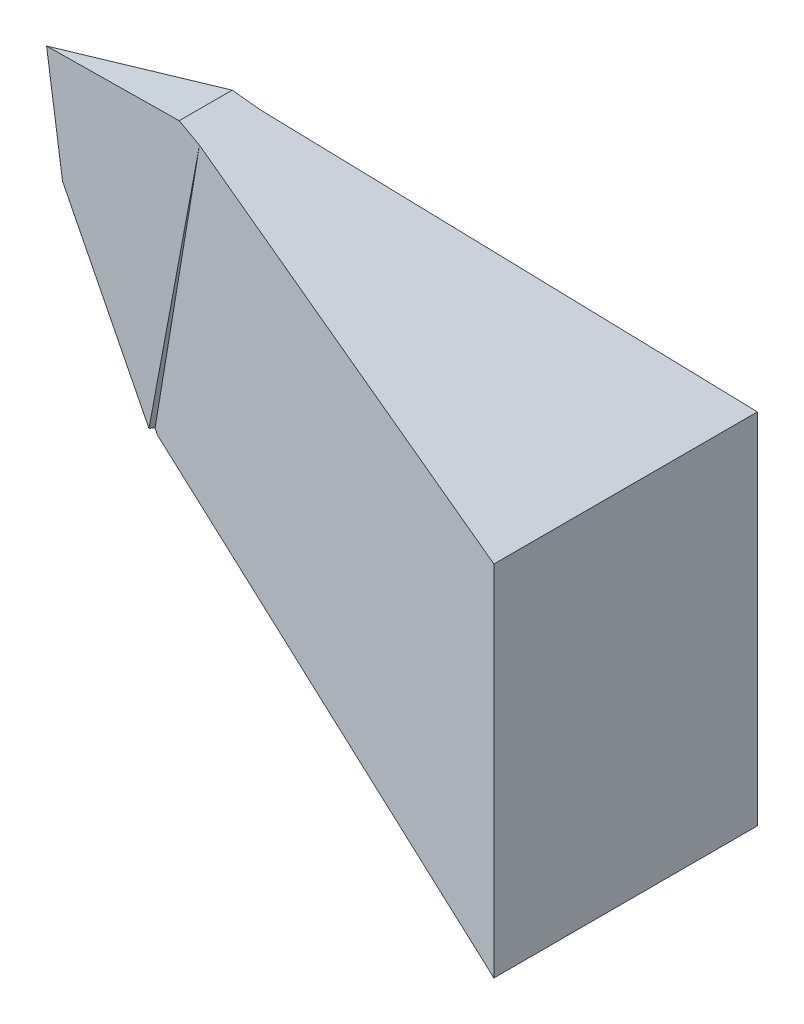
SolidWorks part; units mm, degrees
ref_plane "Front Plane" through (0, 0, 0) normal (0, 0, 1) x (1, 0, 0)
ref_plane "Top Plane" through (0, 0, 0) normal (0, 1, 0) x (1, 0, 0)
ref_plane "Right Plane" through (0, 0, 0) normal (1, 0, 0) x (0, 0, -1)
sketch "Sketch1" plane through (0, 0, 0) normal (0, 0, 1) x (1, 0, 0)
  line L0 (0, 0) -> (-2819.61, 1161.48)
  line L1 (-2819.61, 1161.48) -> (-3490.66, 2155.96)
  line L2 (-3490.66, 2155.96) -> (-3609.78, 2815.96)
  line L3 (0, 0) -> (0, 2235)
  line L4 (0, 2235) -> (-2618, 2991)
  line L5 (-2618, 2991) -> (-3609.78, 2815.96)
  dimension "D1" = 2819.61
  dimension "D2" = 1161.48
  dimension "D3" = 994.48
  dimension "D4" = 671.05
  dimension "D5" = 660
  dimension "D6" = 119.12
  dimension "D7" = 2235
  dimension "D8" = 2618
  dimension "D9" = 756
extrude "Boss-Extrude1" add sketch "Sketch1" along normal blind 821.33 and the other way blind 821.33
ref_plane "Plane1" through (-3609.78, 0, 0) normal (1, 0, 0) x (0, 0, -1)
sketch "Sketch3" plane through (0, 0, 0) normal (-0.3809, -0.9246, 0) x (0.9246, -0.3809, 0)
  line L0 (-3049.4649, 0) -> (-3049.4649, 100)
  line L1 (-3049.4649, -821.33) -> (-3049.4649, 821.33) construction
  line L2 (-3049.4649, 0) -> (-3049.4649, -100)
  line L3 (0, 821.33) -> (-3049.4649, 100)
  line L4 (0, -821.33) -> (-3049.4649, -100)
  dimension "D1" = 100
ref_plane "Plane2" through (-197.2108, 0, 770.8783) normal (0.2478, 0, -0.9688) x (-0.9688, 0, -0.2478)
sketch "Sketch4" plane through (-197.2108, 0, 770.8783) normal (0.2478, 0, -0.9688) x (-0.9688, 0, -0.2478)
  line L0 (2731.6378, 1161.48) -> (2332.756, 2991)
  line L1 (2935.1998, 1161.48) -> (2528.0758, 1161.48) construction
  line L2 (2332.756, 2991) -> (-203.562, 2235)
  line L3 (-203.562, 2235) -> (-203.562, 0)
  line L4 (-203.562, 0) -> (2731.6378, 1161.48)
extrude "Cut-Extrude1" cut sketch "Sketch4" against normal blind 1930.33
ref_plane "Plane3" through (-197.2108, 0, -770.8783) normal (-0.2478, 0, -0.9688) x (-0.9688, 0, 0.2478)
sketch "Sketch5" plane through (-197.2108, 0, -770.8783) normal (-0.2478, 0, -0.9688) x (-0.9688, 0, 0.2478)
  line L0 (-203.562, 0) -> (-203.562, 2235)
  line L1 (-203.562, 2235) -> (2332.756, 2991)
  line L2 (2332.756, 2991) -> (2706.8534, 1161.48)
  line L3 (-203.562, 0) -> (2706.8534, 1161.48) construction
  line L4 (2706.8534, 1161.48) -> (-203.562, 0)
  point P4 (0, 0)
  point P10 (2706.8534, 1161.48)
extrude "Cut-Extrude2" cut sketch "Sketch5" along normal blind 3500.33
sketch "Sketch6" plane through (-591.0222, 3348.7428, 0) normal (-0.1738, 0.9848, 0) x (0.9848, 0.1738, 0)
  line L0 (-3065.4129, 0) -> (-1916.1408, 190.4918)
  line L1 (-3065.4129, 821.33) -> (-3065.4129, -821.33) construction
  line L2 (-1916.1408, 190.4918) -> (-1916.1408, 1255.1015)
  line L3 (-1916.1408, 1255.1015) -> (-3065.4129, 1255.1015)
  line L4 (-3065.4129, 1255.1015) -> (-3065.4129, 0)
  line L5 (-3065.4129, -1489.9437) -> (-2058.3049, -1489.9437)
  line L6 (-2058.3049, -1489.9437) -> (-1916.6486, -190.3528)
  line L7 (-3065.4129, 0) -> (-3065.4129, -1489.9437)
  line L8 (-1916.6486, -190.3528) -> (-3065.4129, 0)
  point P9 (-1916.1408, -190.3528)
sketch "Sketch7" plane through (0, 0, 0) normal (0, 1, 0) x (1, 0, 0)
  line L0 (-3609.78, 0) -> (-2465.8862, 190.4918)
  line L1 (-2465.8862, 190.4918) -> (-2674.0673, 1440.6089)
  line L2 (-2674.0673, 1440.6089) -> (-3609.78, 1440.6089)
  line L3 (-3609.78, 1440.6089) -> (-3609.78, 0)
  line L4 (-3609.78, 0) -> (-3609.78, -1179.2038)
  line L5 (-3609.78, 0) -> (-3609.78, -1489.9437) construction
  line L6 (-3609.78, -1179.2038) -> (-2465.8862, -1179.2038)
  line L7 (-2465.8862, -1179.2038) -> (-2466.4296, -190.3528)
  line L8 (-2466.4296, -190.3528) -> (-3609.78, 0)
extrude "Cut-Extrude4" cut sketch "Sketch7" along normal blind 3500.33 contours L7 L8 L4 L6 | L2 L3 L0 L1 region at (-3098.9949, 0, -743.0567) region at (-3054.7081, 0, 635.8437)
